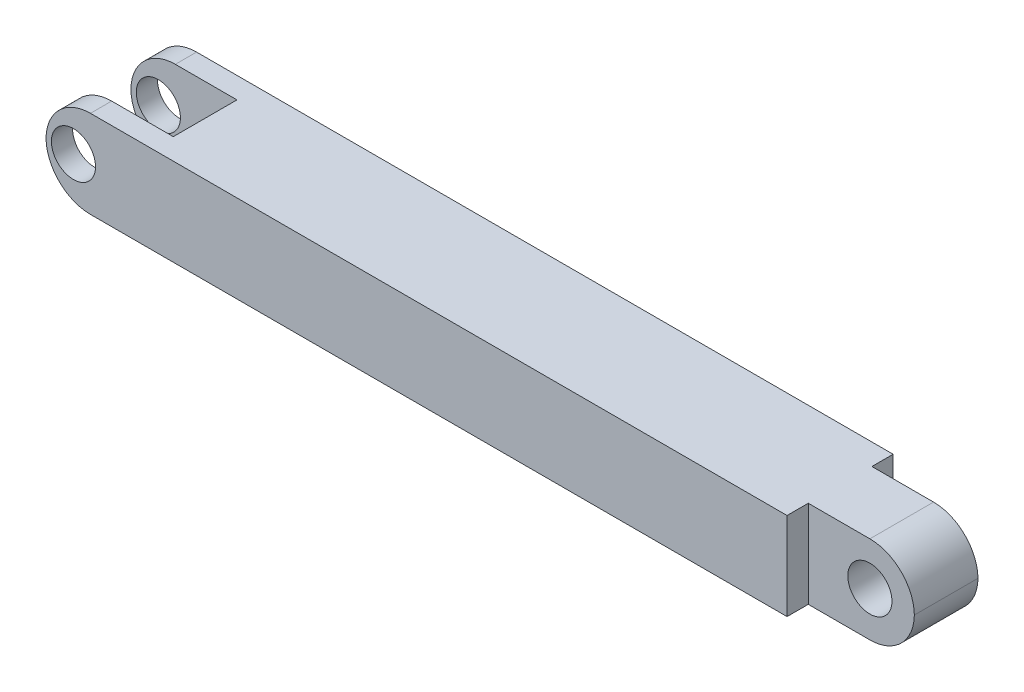
SolidWorks part; units mm, degrees
ref_plane "Front Plane" through (0, 0, 0) normal (0, 0, 1) x (1, 0, 0)
ref_plane "Top Plane" through (0, 0, 0) normal (0, 1, 0) x (1, 0, 0)
ref_plane "Right Plane" through (0, 0, 0) normal (1, 0, 0) x (0, 0, -1)
sketch "Sketch1" plane through (0, 0, 0) normal (0, 1, 0) x (1, 0, 0)
  line L0 (0, 0) -> (69.85, 0)
  line L1 (0, 0) -> (0, -1.999)
  line L2 (0, -1.999) -> (10, -1.999)
  line L3 (0, 0) -> (0, -1.999)
  line L4 (0, -10) -> (0, -8.001)
  line L5 (0, -8.001) -> (10, -8.001)
  line L6 (10, -8.001) -> (10, -1.999)
  line L7 (0, -10) -> (69.85, -10)
  line L8 (0, -8.001) -> (0, -10)
  line L10 (69.85, 0) -> (69.85, -2)
  line L11 (69.85, -2) -> (79.85, -2)
  line L12 (79.85, -2) -> (79.85, -8)
  line L13 (79.85, -8) -> (69.85, -8)
  line L14 (69.85, -8) -> (69.85, -10)
  dimension "D1" = 69.85
  dimension "D2" = 1.999
  dimension "D3" = 10
  dimension "D4" = 10
  dimension "D5" = 1.999
  dimension "D6" = 69.85
  dimension "D7" = 2
  dimension "D8" = 2
extrude "Boss-Extrude1" add sketch "Sketch1" along normal blind 8.255 contours L14 L13 L12 L11 L10 L0 L1 L2 L6 L5 L4 L7 region at (40.926, 0, 5)
fillet "Fillet1" radius 4.191 4 edges at (0, 0, 0.9995) (0, 0, 9.0005) (0, 8.255, 0.9995) (0, 8.255, 9.0005)
sketch "Sketch2" plane through (0, 0, 10) normal (0, 0, 1) x (1, 0, 0)
  circle A1 centre (2.5875, 4.1275) radius 2.079
  dimension "D2" = 4.158
extrude "Cut-Extrude1" cut sketch "Sketch2" against normal through all
fillet "Fillet2" radius 4.191 2 edges at (79.85, 0, 5) (79.85, 8.255, 5)
sketch "Sketch3" plane through (0, 0, 8) normal (0, 0, 1) x (1, 0, 0)
  circle A0 centre (75.659, 4.191) radius 2.079
  dimension "D1" = 4.158
extrude "Cut-Extrude2" cut sketch "Sketch3" against normal blind 8.255
